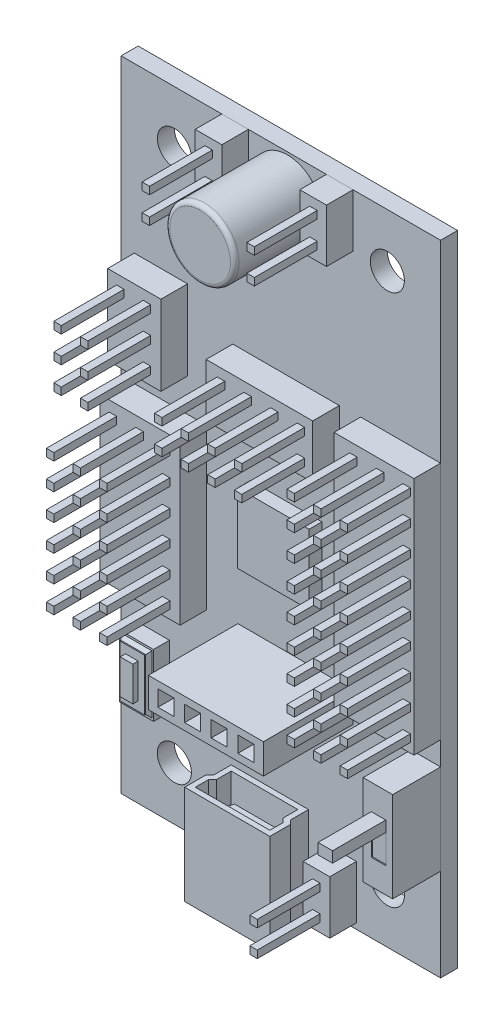
SolidWorks part; units mm, degrees
ref_plane "Plan de face" through (0, 0, 0) normal (0, 0, 1) x (1, 0, 0)
ref_plane "Plan de dessus" through (0, 0, 0) normal (0, 1, 0) x (1, 0, 0)
ref_plane "Plan de droite" through (0, 0, 0) normal (1, 0, 0) x (0, 0, -1)
sketch "Esquisse1" plane through (0, 0, 0) normal (0, 0, 1) x (1, 0, 0)
  line L1 (0, 0) -> (30, 0)
  line L2 (0, 0) -> (0, 60)
  line L3 (0, 60) -> (30, 60)
  line L4 (30, 0) -> (30, 60)
  dimension "D1" = 30
  dimension "D2" = 60
extrude "Boss.-Extru.1" add sketch "Esquisse1" along normal blind 1.6
sketch "Esquisse2" plane through (0, 0, 1.6) normal (0, 0, 1) x (1, 0, 0)
  line L0 (30, 60) -> (0, 60) construction
  line L1 (0, 60) -> (0, 0) construction
  circle A0 centre (5, 55) radius 1.6
  circle A1 centre (25, 55) radius 1.6
  circle A2 centre (25, 5) radius 1.6
  circle A3 centre (5, 5) radius 1.6
  dimension "D1" = 3.2
  dimension "D4" = 20
  dimension "D5" = 50
  dimension "D2" = 5
  dimension "D3" = 5
extrude "Enlèv. mat.-Extru.1" cut sketch "Esquisse2" against normal blind 1.6
sketch "Esquisse3" plane through (0, 0, 1.6) normal (0, 0, 1) x (1, 0, 0)
  line L0 (26.4667, 40.9408) -> (27.1667, 40.9408)
  line L1 (23.9667, 40.9408) -> (24.6667, 40.9408)
  line L2 (23.9667, 40.9408) -> (23.9667, 40.2408)
  line L3 (23.9667, 40.2408) -> (24.6667, 40.2408)
  line L4 (24.6667, 40.9408) -> (24.6667, 40.2408)
  line L5 (26.4667, 40.9408) -> (26.4667, 40.2408)
  line L6 (26.4667, 40.2408) -> (27.1667, 40.2408)
  line L7 (27.1667, 40.9408) -> (27.1667, 40.2408)
  line L8 (28.9667, 40.9408) -> (29.6667, 40.9408)
  line L9 (28.9667, 40.9408) -> (28.9667, 40.2408)
  line L10 (28.9667, 40.2408) -> (29.6667, 40.2408)
  line L11 (29.6667, 40.9408) -> (29.6667, 40.2408)
  line L12 (23.9667, 38.4408) -> (24.6667, 38.4408)
  line L13 (23.9667, 38.4408) -> (23.9667, 37.7408)
  line L14 (23.9667, 37.7408) -> (24.6667, 37.7408)
  line L15 (24.6667, 38.4408) -> (24.6667, 37.7408)
  line L16 (26.4667, 38.4408) -> (27.1667, 38.4408)
  line L17 (26.4667, 38.4408) -> (26.4667, 37.7408)
  line L18 (26.4667, 37.7408) -> (27.1667, 37.7408)
  line L19 (27.1667, 38.4408) -> (27.1667, 37.7408)
  line L20 (28.9667, 38.4408) -> (29.6667, 38.4408)
  line L21 (28.9667, 38.4408) -> (28.9667, 37.7408)
  line L22 (28.9667, 37.7408) -> (29.6667, 37.7408)
  line L23 (29.6667, 38.4408) -> (29.6667, 37.7408)
  line L24 (23.9667, 35.9408) -> (24.6667, 35.9408)
  line L25 (23.9667, 35.9408) -> (23.9667, 35.2408)
  line L26 (23.9667, 35.2408) -> (24.6667, 35.2408)
  line L27 (24.6667, 35.9408) -> (24.6667, 35.2408)
  line L28 (26.4667, 35.9408) -> (27.1667, 35.9408)
  line L29 (26.4667, 35.9408) -> (26.4667, 35.2408)
  line L30 (26.4667, 35.2408) -> (27.1667, 35.2408)
  line L31 (27.1667, 35.9408) -> (27.1667, 35.2408)
  line L32 (28.9667, 35.9408) -> (29.6667, 35.9408)
  line L33 (28.9667, 35.9408) -> (28.9667, 35.2408)
  line L34 (28.9667, 35.2408) -> (29.6667, 35.2408)
  line L35 (29.6667, 35.9408) -> (29.6667, 35.2408)
  line L36 (23.9667, 33.4408) -> (24.6667, 33.4408)
  line L37 (23.9667, 33.4408) -> (23.9667, 32.7408)
  line L38 (23.9667, 32.7408) -> (24.6667, 32.7408)
  line L39 (24.6667, 33.4408) -> (24.6667, 32.7408)
  line L40 (26.4667, 33.4408) -> (27.1667, 33.4408)
  line L41 (26.4667, 33.4408) -> (26.4667, 32.7408)
  line L42 (26.4667, 32.7408) -> (27.1667, 32.7408)
  line L43 (27.1667, 33.4408) -> (27.1667, 32.7408)
  line L44 (28.9667, 33.4408) -> (29.6667, 33.4408)
  line L45 (28.9667, 33.4408) -> (28.9667, 32.7408)
  line L46 (28.9667, 32.7408) -> (29.6667, 32.7408)
  line L47 (29.6667, 33.4408) -> (29.6667, 32.7408)
  line L48 (23.9667, 30.9408) -> (24.6667, 30.9408)
  line L49 (23.9667, 30.9408) -> (23.9667, 30.2408)
  line L50 (23.9667, 30.2408) -> (24.6667, 30.2408)
  line L51 (24.6667, 30.9408) -> (24.6667, 30.2408)
  line L52 (26.4667, 30.9408) -> (27.1667, 30.9408)
  line L53 (26.4667, 30.9408) -> (26.4667, 30.2408)
  line L54 (26.4667, 30.2408) -> (27.1667, 30.2408)
  line L55 (27.1667, 30.9408) -> (27.1667, 30.2408)
  line L56 (28.9667, 30.9408) -> (29.6667, 30.9408)
  line L57 (28.9667, 30.9408) -> (28.9667, 30.2408)
  line L58 (28.9667, 30.2408) -> (29.6667, 30.2408)
  line L59 (29.6667, 30.9408) -> (29.6667, 30.2408)
  line L60 (23.9667, 28.4408) -> (24.6667, 28.4408)
  line L61 (23.9667, 28.4408) -> (23.9667, 27.7408)
  line L62 (23.9667, 27.7408) -> (24.6667, 27.7408)
  line L63 (24.6667, 28.4408) -> (24.6667, 27.7408)
  line L64 (26.4667, 28.4408) -> (27.1667, 28.4408)
  line L65 (26.4667, 28.4408) -> (26.4667, 27.7408)
  line L66 (26.4667, 27.7408) -> (27.1667, 27.7408)
  line L67 (27.1667, 28.4408) -> (27.1667, 27.7408)
  line L68 (28.9667, 28.4408) -> (29.6667, 28.4408)
  line L69 (28.9667, 28.4408) -> (28.9667, 27.7408)
  line L70 (28.9667, 27.7408) -> (29.6667, 27.7408)
  line L71 (29.6667, 28.4408) -> (29.6667, 27.7408)
  line L72 (23.9667, 25.9408) -> (24.6667, 25.9408)
  line L73 (23.9667, 25.9408) -> (23.9667, 25.2408)
  line L74 (23.9667, 25.2408) -> (24.6667, 25.2408)
  line L75 (24.6667, 25.9408) -> (24.6667, 25.2408)
  line L76 (26.4667, 25.9408) -> (27.1667, 25.9408)
  line L77 (26.4667, 25.9408) -> (26.4667, 25.2408)
  line L78 (26.4667, 25.2408) -> (27.1667, 25.2408)
  line L79 (27.1667, 25.9408) -> (27.1667, 25.2408)
  line L80 (28.9667, 25.9408) -> (29.6667, 25.9408)
  line L81 (28.9667, 25.9408) -> (28.9667, 25.2408)
  line L82 (28.9667, 25.2408) -> (29.6667, 25.2408)
  line L83 (29.6667, 25.9408) -> (29.6667, 25.2408)
  line L84 (23.9667, 23.4408) -> (24.6667, 23.4408)
  line L85 (23.9667, 23.4408) -> (23.9667, 22.7408)
  line L86 (23.9667, 22.7408) -> (24.6667, 22.7408)
  line L87 (24.6667, 23.4408) -> (24.6667, 22.7408)
  line L88 (26.4667, 23.4408) -> (27.1667, 23.4408)
  line L89 (26.4667, 23.4408) -> (26.4667, 22.7408)
  line L90 (26.4667, 22.7408) -> (27.1667, 22.7408)
  line L91 (27.1667, 23.4408) -> (27.1667, 22.7408)
  line L92 (28.9667, 23.4408) -> (29.6667, 23.4408)
  line L93 (28.9667, 23.4408) -> (28.9667, 22.7408)
  line L94 (28.9667, 22.7408) -> (29.6667, 22.7408)
  line L95 (29.6667, 23.4408) -> (29.6667, 22.7408)
  line L96 (23.9667, 20.9408) -> (24.6667, 20.9408)
  line L97 (23.9667, 20.9408) -> (23.9667, 20.2408)
  line L98 (23.9667, 20.2408) -> (24.6667, 20.2408)
  line L99 (24.6667, 20.9408) -> (24.6667, 20.2408)
  line L100 (26.4667, 20.9408) -> (27.1667, 20.9408)
  line L101 (26.4667, 20.9408) -> (26.4667, 20.2408)
  line L102 (26.4667, 20.2408) -> (27.1667, 20.2408)
  line L103 (27.1667, 20.9408) -> (27.1667, 20.2408)
  line L104 (28.9667, 20.9408) -> (29.6667, 20.9408)
  line L105 (28.9667, 20.9408) -> (28.9667, 20.2408)
  line L106 (28.9667, 20.2408) -> (29.6667, 20.2408)
  line L107 (29.6667, 20.9408) -> (29.6667, 20.2408)
  line L108 (3.8796, 32.9726) -> (4.5796, 32.9726)
  line L109 (1.3796, 32.9726) -> (2.0796, 32.9726)
  line L110 (1.3796, 32.9726) -> (1.3796, 32.2726)
  line L111 (1.3796, 32.2726) -> (2.0796, 32.2726)
  line L112 (2.0796, 32.9726) -> (2.0796, 32.2726)
  line L113 (3.8796, 32.9726) -> (3.8796, 32.2726)
  line L114 (3.8796, 32.2726) -> (4.5796, 32.2726)
  line L115 (4.5796, 32.9726) -> (4.5796, 32.2726)
  line L116 (6.3796, 32.9726) -> (7.0796, 32.9726)
  line L117 (6.3796, 32.9726) -> (6.3796, 32.2726)
  line L118 (6.3796, 32.2726) -> (7.0796, 32.2726)
  line L119 (7.0796, 32.9726) -> (7.0796, 32.2726)
  line L120 (1.3796, 30.4726) -> (2.0796, 30.4726)
  line L121 (1.3796, 30.4726) -> (1.3796, 29.7726)
  line L122 (1.3796, 29.7726) -> (2.0796, 29.7726)
  line L123 (2.0796, 30.4726) -> (2.0796, 29.7726)
  line L124 (3.8796, 30.4726) -> (4.5796, 30.4726)
  line L125 (3.8796, 30.4726) -> (3.8796, 29.7726)
  line L126 (3.8796, 29.7726) -> (4.5796, 29.7726)
  line L127 (4.5796, 30.4726) -> (4.5796, 29.7726)
  line L128 (6.3796, 30.4726) -> (7.0796, 30.4726)
  line L129 (6.3796, 30.4726) -> (6.3796, 29.7726)
  line L130 (6.3796, 29.7726) -> (7.0796, 29.7726)
  line L131 (7.0796, 30.4726) -> (7.0796, 29.7726)
  line L132 (1.3796, 27.9726) -> (2.0796, 27.9726)
  line L133 (1.3796, 27.9726) -> (1.3796, 27.2726)
  line L134 (1.3796, 27.2726) -> (2.0796, 27.2726)
  line L135 (2.0796, 27.9726) -> (2.0796, 27.2726)
  line L136 (3.8796, 27.9726) -> (4.5796, 27.9726)
  line L137 (3.8796, 27.9726) -> (3.8796, 27.2726)
  line L138 (3.8796, 27.2726) -> (4.5796, 27.2726)
  line L139 (4.5796, 27.9726) -> (4.5796, 27.2726)
  line L140 (6.3796, 27.9726) -> (7.0796, 27.9726)
  line L141 (6.3796, 27.9726) -> (6.3796, 27.2726)
  line L142 (6.3796, 27.2726) -> (7.0796, 27.2726)
  line L143 (7.0796, 27.9726) -> (7.0796, 27.2726)
  line L144 (1.3796, 25.4726) -> (2.0796, 25.4726)
  line L145 (1.3796, 25.4726) -> (1.3796, 24.7726)
  line L146 (1.3796, 24.7726) -> (2.0796, 24.7726)
  line L147 (2.0796, 25.4726) -> (2.0796, 24.7726)
  line L148 (3.8796, 25.4726) -> (4.5796, 25.4726)
  line L149 (3.8796, 25.4726) -> (3.8796, 24.7726)
  line L150 (3.8796, 24.7726) -> (4.5796, 24.7726)
  line L151 (4.5796, 25.4726) -> (4.5796, 24.7726)
  line L152 (6.3796, 25.4726) -> (7.0796, 25.4726)
  line L153 (6.3796, 25.4726) -> (6.3796, 24.7726)
  line L154 (6.3796, 24.7726) -> (7.0796, 24.7726)
  line L155 (7.0796, 25.4726) -> (7.0796, 24.7726)
  line L156 (1.3796, 22.9726) -> (2.0796, 22.9726)
  line L157 (1.3796, 22.9726) -> (1.3796, 22.2726)
  line L158 (1.3796, 22.2726) -> (2.0796, 22.2726)
  line L159 (2.0796, 22.9726) -> (2.0796, 22.2726)
  line L160 (3.8796, 22.9726) -> (4.5796, 22.9726)
  line L161 (3.8796, 22.9726) -> (3.8796, 22.2726)
  line L162 (3.8796, 22.2726) -> (4.5796, 22.2726)
  line L163 (4.5796, 22.9726) -> (4.5796, 22.2726)
  line L164 (6.3796, 22.9726) -> (7.0796, 22.9726)
  line L165 (6.3796, 22.9726) -> (6.3796, 22.2726)
  line L166 (6.3796, 22.2726) -> (7.0796, 22.2726)
  line L167 (7.0796, 22.9726) -> (7.0796, 22.2726)
  line L168 (1.3796, 20.4726) -> (2.0796, 20.4726)
  line L169 (1.3796, 20.4726) -> (1.3796, 19.7726)
  line L170 (1.3796, 19.7726) -> (2.0796, 19.7726)
  line L171 (2.0796, 20.4726) -> (2.0796, 19.7726)
  line L172 (3.8796, 20.4726) -> (4.5796, 20.4726)
  line L173 (3.8796, 20.4726) -> (3.8796, 19.7726)
  line L174 (3.8796, 19.7726) -> (4.5796, 19.7726)
  line L175 (4.5796, 20.4726) -> (4.5796, 19.7726)
  line L176 (6.3796, 20.4726) -> (7.0796, 20.4726)
  line L177 (6.3796, 20.4726) -> (6.3796, 19.7726)
  line L178 (6.3796, 19.7726) -> (7.0796, 19.7726)
  line L179 (7.0796, 20.4726) -> (7.0796, 19.7726)
  line L180 (10.3663, 56.6272) -> (11.0663, 56.6272)
  line L181 (10.3663, 59.1272) -> (11.0663, 59.1272)
  line L182 (10.3663, 59.1272) -> (10.3663, 58.4272)
  line L183 (10.3663, 58.4272) -> (11.0663, 58.4272)
  line L184 (11.0663, 59.1272) -> (11.0663, 58.4272)
  line L185 (20.2099, 59.1272) -> (20.9099, 59.1272)
  line L186 (20.2099, 59.1272) -> (20.2099, 58.4272)
  line L187 (20.2099, 58.4272) -> (20.9099, 58.4272)
  line L188 (20.9099, 59.1272) -> (20.9099, 58.4272)
  line L189 (10.3663, 56.6272) -> (10.3663, 55.9272)
  line L190 (10.3663, 55.9272) -> (11.0663, 55.9272)
  line L191 (11.0663, 56.6272) -> (11.0663, 55.9272)
  line L192 (20.2099, 56.6272) -> (20.9099, 56.6272)
  line L193 (20.2099, 56.6272) -> (20.2099, 55.9272)
  line L194 (20.2099, 55.9272) -> (20.9099, 55.9272)
  line L195 (20.9099, 56.6272) -> (20.9099, 55.9272)
  line L196 (20.4843, 4.5631) -> (21.1843, 4.5631)
  line L197 (20.4843, 2.0631) -> (21.1843, 2.0631)
  line L198 (20.4843, 2.0631) -> (20.4843, 1.3631)
  line L199 (20.4843, 1.3631) -> (21.1843, 1.3631)
  line L200 (21.1843, 2.0631) -> (21.1843, 1.3631)
  line L201 (20.4843, 4.5631) -> (20.4843, 3.8631)
  line L202 (20.4843, 3.8631) -> (21.1843, 3.8631)
  line L203 (21.1843, 4.5631) -> (21.1843, 3.8631)
  line L204 (4.5759, 38.6498) -> (5.2759, 38.6498)
  line L205 (2.0759, 38.6498) -> (2.7759, 38.6498)
  line L206 (2.0759, 38.6498) -> (2.0759, 37.9498)
  line L207 (2.0759, 37.9498) -> (2.7759, 37.9498)
  line L208 (2.7759, 38.6498) -> (2.7759, 37.9498)
  line L209 (4.5759, 38.6498) -> (4.5759, 37.9498)
  line L210 (4.5759, 37.9498) -> (5.2759, 37.9498)
  line L211 (5.2759, 38.6498) -> (5.2759, 37.9498)
  line L212 (2.0759, 41.1498) -> (2.7759, 41.1498)
  line L213 (2.0759, 41.1498) -> (2.0759, 40.4498)
  line L214 (2.0759, 40.4498) -> (2.7759, 40.4498)
  line L215 (2.7759, 41.1498) -> (2.7759, 40.4498)
  line L216 (4.5759, 41.1498) -> (5.2759, 41.1498)
  line L217 (4.5759, 41.1498) -> (4.5759, 40.4498)
  line L218 (4.5759, 40.4498) -> (5.2759, 40.4498)
  line L219 (5.2759, 41.1498) -> (5.2759, 40.4498)
  line L220 (2.0759, 43.6498) -> (2.7759, 43.6498)
  line L221 (2.0759, 43.6498) -> (2.0759, 42.9498)
  line L222 (2.0759, 42.9498) -> (2.7759, 42.9498)
  line L223 (2.7759, 43.6498) -> (2.7759, 42.9498)
  line L224 (4.5759, 43.6498) -> (5.2759, 43.6498)
  line L225 (4.5759, 43.6498) -> (4.5759, 42.9498)
  line L226 (4.5759, 42.9498) -> (5.2759, 42.9498)
  line L227 (5.2759, 43.6498) -> (5.2759, 42.9498)
  line L228 (14.0333, 38.4009) -> (14.7333, 38.4009)
  line L229 (11.5333, 38.4009) -> (12.2333, 38.4009)
  line L230 (11.5333, 38.4009) -> (11.5333, 37.7009)
  line L231 (11.5333, 37.7009) -> (12.2333, 37.7009)
  line L232 (12.2333, 38.4009) -> (12.2333, 37.7009)
  line L233 (14.0333, 38.4009) -> (14.0333, 37.7009)
  line L234 (14.0333, 37.7009) -> (14.7333, 37.7009)
  line L235 (14.7333, 38.4009) -> (14.7333, 37.7009)
  line L236 (16.5333, 38.4009) -> (17.2333, 38.4009)
  line L237 (16.5333, 38.4009) -> (16.5333, 37.7009)
  line L238 (16.5333, 37.7009) -> (17.2333, 37.7009)
  line L239 (17.2333, 38.4009) -> (17.2333, 37.7009)
  line L240 (19.0333, 38.4009) -> (19.7333, 38.4009)
  line L241 (19.0333, 38.4009) -> (19.0333, 37.7009)
  line L242 (19.0333, 37.7009) -> (19.7333, 37.7009)
  line L243 (19.7333, 38.4009) -> (19.7333, 37.7009)
  line L244 (11.5333, 40.9009) -> (12.2333, 40.9009)
  line L245 (11.5333, 40.9009) -> (11.5333, 40.2009)
  line L246 (11.5333, 40.2009) -> (12.2333, 40.2009)
  line L247 (12.2333, 40.9009) -> (12.2333, 40.2009)
  line L248 (14.0333, 40.9009) -> (14.7333, 40.9009)
  line L249 (14.0333, 40.9009) -> (14.0333, 40.2009)
  line L250 (14.0333, 40.2009) -> (14.7333, 40.2009)
  line L251 (14.7333, 40.9009) -> (14.7333, 40.2009)
  line L252 (16.5333, 40.9009) -> (17.2333, 40.9009)
  line L253 (16.5333, 40.9009) -> (16.5333, 40.2009)
  line L254 (16.5333, 40.2009) -> (17.2333, 40.2009)
  line L255 (17.2333, 40.9009) -> (17.2333, 40.2009)
  line L256 (19.0333, 40.9009) -> (19.7333, 40.9009)
  line L257 (19.0333, 40.9009) -> (19.0333, 40.2009)
  line L258 (19.0333, 40.2009) -> (19.7333, 40.2009)
  line L259 (19.7333, 40.9009) -> (19.7333, 40.2009)
  dimension "D1" = 0.7
  dimension "D4" = 2.5
  dimension "D5" = 2.5
  dimension "D8" = 2.5
  dimension "D9" = 2.5
  dimension "D2" = 3
  dimension "D3" = 9
  dimension "D6" = 3
  dimension "D7" = 6
  dimension "D10" = 2
  dimension "D11" = 2
  dimension "D12" = 2
  dimension "D13" = 3
  dimension "D14" = 4
  dimension "D15" = 2
extrude "Boss.-Extru.2" add sketch "Esquisse3" along normal blind 8.4
sketch "Esquisse4" plane through (0, 0, 1.6) normal (0, 0, 1) x (1, 0, 0)
  line L0 (30, 60) -> (0, 60) construction
  line L1 (9.455, 55) -> (11.955, 55)
  line L2 (9.455, 55) -> (9.455, 60)
  line L3 (9.455, 60) -> (11.955, 60)
  line L4 (11.955, 55) -> (11.955, 60)
  line L5 (30, 0) -> (30, 60) construction
  line L6 (19.2807, 60) -> (21.7807, 60)
  line L7 (19.2807, 60) -> (19.2807, 55)
  line L8 (19.2807, 55) -> (21.7807, 55)
  line L9 (21.7807, 60) -> (21.7807, 55)
  line L10 (1.2358, 44.5738) -> (6.2358, 44.5738)
  line L11 (1.2358, 44.5738) -> (1.2358, 37.0738)
  line L12 (1.2358, 37.0738) -> (6.2358, 37.0738)
  line L13 (6.2358, 44.5738) -> (6.2358, 37.0738)
  line L14 (10.4879, 41.802) -> (20.4879, 41.802)
  line L15 (10.4879, 41.802) -> (10.4879, 36.802)
  line L16 (10.4879, 36.802) -> (20.4879, 36.802)
  line L17 (20.4879, 41.802) -> (20.4879, 36.802)
  line L18 (22.5, 41.8716) -> (30, 41.8716)
  line L19 (22.5, 41.8716) -> (22.5, 19.3716)
  line L20 (22.5, 19.3716) -> (30, 19.3716)
  line L21 (30, 41.8716) -> (30, 19.3716)
  line L23 (0.535, 33.9583) -> (8.035, 33.9583)
  line L24 (0.535, 33.9583) -> (0.535, 18.9583)
  line L25 (0.535, 18.9583) -> (8.035, 18.9583)
  line L26 (8.035, 33.9583) -> (8.035, 18.9583)
  line L27 (19.5923, 5.53) -> (22.0923, 5.53)
  line L28 (19.5923, 5.53) -> (19.5923, 0.53)
  line L29 (19.5923, 0.53) -> (22.0923, 0.53)
  line L30 (22.0923, 5.53) -> (22.0923, 0.53)
  dimension "D1" = 2.5
  dimension "D2" = 5
  dimension "D3" = 10
  dimension "D4" = 5
  dimension "D5" = 5
  dimension "D6" = 7.5
  dimension "D7" = 15
  dimension "D8" = 22.5
  dimension "D9" = 5
  dimension "D10" = 2.5
extrude "Boss.-Extru.3" add sketch "Esquisse4" along normal blind 2.5 separate body
sketch "Esquisse5" plane through (0, 0, 1.6) normal (0, 0, 1) x (1, 0, 0)
  line L0 (11.861, 17.9004) -> (10.961, 17.9004) construction
  line L1 (10.961, 19.3004) -> (21.761, 19.3004)
  line L2 (10.961, 19.3004) -> (10.961, 16.5004)
  line L3 (10.961, 16.5004) -> (21.761, 16.5004)
  line L4 (21.761, 19.3004) -> (21.761, 16.5004)
  line L5 (11.861, 18.6504) -> (13.361, 18.6504)
  line L6 (11.861, 18.6504) -> (11.861, 17.1504)
  line L7 (11.861, 17.1504) -> (13.361, 17.1504)
  line L8 (13.361, 18.6504) -> (13.361, 17.1504)
  line L9 (14.361, 18.6504) -> (15.861, 18.6504)
  line L10 (14.361, 18.6504) -> (14.361, 17.1504)
  line L11 (14.361, 17.1504) -> (15.861, 17.1504)
  line L12 (15.861, 18.6504) -> (15.861, 17.1504)
  line L13 (16.861, 18.6504) -> (18.361, 18.6504)
  line L14 (16.861, 18.6504) -> (16.861, 17.1504)
  line L15 (16.861, 17.1504) -> (18.361, 17.1504)
  line L16 (18.361, 18.6504) -> (18.361, 17.1504)
  line L17 (19.361, 18.6504) -> (20.861, 18.6504)
  line L18 (19.361, 18.6504) -> (19.361, 17.1504)
  line L19 (19.361, 17.1504) -> (20.861, 17.1504)
  line L20 (20.861, 18.6504) -> (20.861, 17.1504)
  line L22 (20.861, 17.9004) -> (21.761, 17.9004) construction
  dimension "D1" = 1.5
  dimension "D2" = 2.5
  dimension "D3" = 2.5
  dimension "D4" = 2.5
  dimension "D5" = 2.8
  dimension "D6" = 10.8
extrude "Boss.-Extru.4" add sketch "Esquisse5" along normal blind 8.4 separate body
sketch "Esquisse6" plane through (0, 0, 1.6) normal (0, 0, 1) x (1, 0, 0)
  line L0 (30, 0) -> (30, 60) construction
  line L1 (27.226, 17.165) -> (30, 17.165)
  line L2 (27.226, 17.165) -> (27.226, 8.6811)
  line L3 (27.226, 8.6811) -> (30, 8.6811)
  line L4 (30, 17.165) -> (30, 8.6811)
extrude "Boss.-Extru.5" add sketch "Esquisse6" along normal blind 4.5 separate body
sketch "Esquisse7" plane through (0, 0, 6.1) normal (0, 0, 1) x (1, 0, 0)
  line L1 (27.995, 14.7741) -> (29.3511, 14.7741)
  line L2 (27.995, 14.7741) -> (27.995, 13.7618)
  line L3 (27.995, 13.7618) -> (29.3511, 13.7618)
  line L4 (29.3511, 14.7741) -> (29.3511, 13.7618)
extrude "Boss.-Extru.6" add sketch "Esquisse7" along normal blind 5
sketch "Esquisse8" plane through (0, 0, 0) normal (0, -1, 0) x (1, 0, 0)
  line L0 (10.3373, 1.6) -> (10.3373, 3.2788)
  line L1 (0, 1.6) -> (30, 1.6) construction
  line L2 (10.3373, 3.2788) -> (9.9669, 3.6492)
  line L3 (9.9669, 3.6492) -> (9.9669, 5.6)
  line L4 (9.9669, 5.6) -> (17.9669, 5.6)
  line L5 (17.9669, 5.6) -> (17.9669, 3.6492)
  line L6 (17.9669, 3.6492) -> (17.5964, 3.2788)
  line L7 (17.5964, 3.2788) -> (17.5964, 1.6)
  line L8 (17.5964, 1.6) -> (10.3373, 1.6)
  dimension "D1" = 8
  dimension "D2" = 4
extrude "Extru.-Mince1" add sketch "Esquisse8" against normal blind 7.5 and the other way blind 1.8 separate body thin thin type one direction reverse wall 0.5
sketch "Esquisse9" plane through (0, 0, 0) normal (0, -1, 0) x (1, 0, 0)
  line L0 (11.6875, 2.6314) -> (11.2586, 4.0083)
  line L1 (11.2586, 4.0083) -> (16.745, 4.0083)
  line L2 (16.745, 4.0083) -> (16.113, 2.6314)
  line L3 (16.113, 2.6314) -> (11.6875, 2.6314)
extrude "Boss.-Extru.7" add sketch "Esquisse9" along normal blind 1 and the other way blind 5.5
sketch "Esquisse10" plane through (0, 0, 1.6) normal (0, 0, 1) x (1, 0, 0)
  circle A0 centre (15.6166, 56.5078) radius 3.25
  dimension "D1" = 6.5
extrude "Boss.-Extru.8" add sketch "Esquisse10" along normal blind 8.2
fillet "Congé1" radius 0.4 1 edges at (18.8666, 56.5078, 9.8)
sketch "Esquisse11" plane through (0, 0, 1.6) normal (0, 0, 1) x (1, 0, 0)
  line L1 (12.1433, 31.5314) -> (18.8587, 31.5314)
  line L2 (12.1433, 31.5314) -> (12.1433, 24.9818)
  line L3 (12.1433, 24.9818) -> (18.8587, 24.9818)
  line L4 (18.8587, 31.5314) -> (18.8587, 24.9818)
extrude "Boss.-Extru.9" add sketch "Esquisse11" along normal blind 1.2
sketch "Esquisse12" plane through (0, 0, 1.6) normal (0, 0, 1) x (1, 0, 0)
  line L1 (1.3692, 14.7378) -> (4.5369, 14.7378)
  line L2 (1.3692, 14.7378) -> (1.3692, 8.8844)
  line L3 (1.3692, 8.8844) -> (4.5369, 8.8844)
  line L4 (4.5369, 14.7378) -> (4.5369, 8.8844)
extrude "Boss.-Extru.10" add sketch "Esquisse12" along normal blind 1.5
sketch "Esquisse13" plane through (0, 0, 3.1) normal (0, 0, 1) x (1, 0, 0)
  line L1 (1.7824, 14.2557) -> (4.1008, 14.2557)
  line L2 (1.7824, 14.2557) -> (1.7824, 9.3894)
  line L3 (1.7824, 9.3894) -> (4.1008, 9.3894)
  line L4 (4.1008, 14.2557) -> (4.1008, 9.3894)
extrude "Boss.-Extru.11" add sketch "Esquisse13" along normal blind 0.4
sketch "Esquisse14" plane through (0, 0, 3.5) normal (0, 0, 1) x (1, 0, 0)
  line L1 (2.3104, 13.4753) -> (3.504, 13.4753)
  line L2 (2.3104, 13.4753) -> (2.3104, 10.2387)
  line L3 (2.3104, 10.2387) -> (3.504, 10.2387)
  line L4 (3.504, 13.4753) -> (3.504, 10.2387)
extrude "Boss.-Extru.12" add sketch "Esquisse14" along normal blind 0.5
chamfer "Chanfrein1" distance 0.3 angle 45 4 edges at (2.9416, 14.2557, 3.1) (4.1008, 11.8226, 3.1) (2.9416, 9.3894, 3.1) (1.7824, 11.8226, 3.1)
sketch "Esquisse15" plane through (0, 0, 6.1) normal (0, 0, 1) x (1, 0, 0)
  line L1 (27.995, 13.7618) -> (29.3511, 13.7618)
  line L2 (27.995, 13.7618) -> (27.995, 11.0662)
  line L3 (27.995, 11.0662) -> (29.3511, 11.0662)
  line L4 (29.3511, 13.7618) -> (29.3511, 11.0662)
  line L5 (27.995, 13.7618) -> (29.3511, 13.7618) construction
extrude "Enlèv. mat.-Extru.3" cut sketch "Esquisse15" against normal blind 0.1
